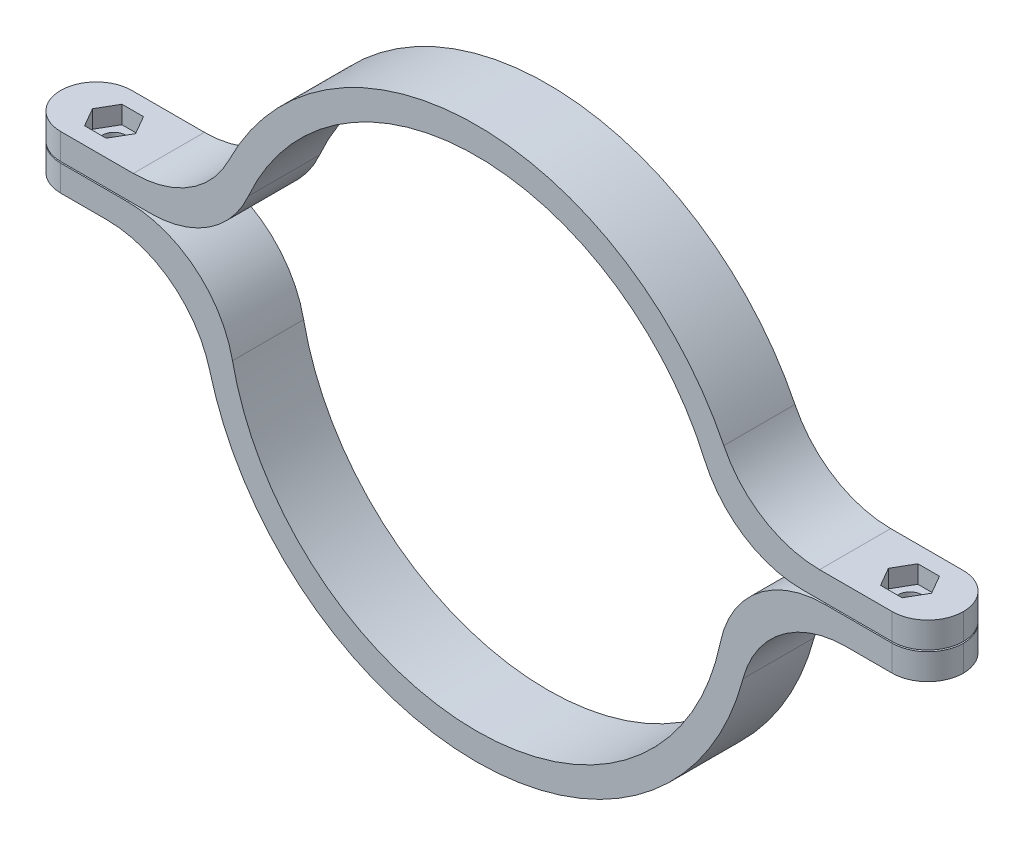
SolidWorks part; units mm, degrees
ref_plane "Front Plane" through (0, 0, 0) normal (0, 0, 1) x (1, 0, 0)
ref_plane "Top Plane" through (0, 0, 0) normal (0, 1, 0) x (1, 0, 0)
ref_plane "Right Plane" through (0, 0, 0) normal (1, 0, 0) x (0, 0, -1)
sketch "Sketch2" plane through (0, 0, 0) normal (0, 0, 1) x (1, 0, 0)
  line L1 (-126.8521, 2.5) -> (126.8521, 2.5)
  line L2 (-126.8521, 2.5) -> (-126.8521, 17.5)
  line L3 (-126.8521, 10) -> (-76.8521, 10)
  line L4 (0, 0) -> (0, 38.05)
  line L5 (-185.0643, 17.5) -> (178.4815, 17.5)
  line L6 (126.8521, 10) -> (76.8521, 10)
  line L7 (126.8521, 2.5) -> (126.8521, 17.5)
  line L8 (-76.8521, 10) -> (76.8521, 10)
  circle A0 centre (0, 0) radius 70 construction
  circle A1 centre (0, 0) radius 70
  circle A2 centre (0, 0) radius 77.5
  circle M7 centre (0, 0) radius 70
  dimension "D2" = 7.5
  dimension "D3" = 50
  dimension "D1" = 7.5
extrude "Boss-Extrude1" add sketch "Sketch2" against normal blind 20 contours A2 M7 | L8 A2 M7 | A2 L3 L2 | A2 L5 L2 L3 | L5 A2 L8 M7 | L5 A2 M7 | L8 A2 L5 M7 | A2 L6 L7 L5 | A2 L7 L6 | A2 L8 M7 region at (-102.0343, 6.2576, 0) region at (-73.4513, 6.2555, 0) region at (-73.7075, 0.7557, 0) region at (-101.5439, 13.7667, 0) region at (-72.4174, 13.7623, 0) region at (0, 75.8752, 0) region at (102.0343, 6.2576, 0) region at (73.4513, 6.2555, 0) region at (72.4174, 13.7623, 0) region at (101.5439, 13.7667, 0)
sketch "Sketch4" plane through (-126.8521, 0, 0) normal (-1, 0, 0) x (0, 0, 1)
  line L0 (-20, 10) -> (0, 10) construction
  line L1 (-20, 9.8) -> (0, 9.8)
  line L2 (-20, 10.2) -> (0, 10.2)
  line L3 (-20, 10.2) -> (-20, 9.8)
  line L4 (0, 2.5) -> (0, 17.5)
  line L5 (0, 17.5) -> (-20, 17.5)
  line L6 (-20, 17.5) -> (-20, 2.5)
  line L7 (-20, 2.5) -> (0, 2.5)
  line L8 (0, 2.5) -> (0, 17.5) construction
  line L9 (0, 17.5) -> (-20, 17.5) construction
  line L10 (-20, 17.5) -> (-20, 2.5) construction
  line L12 (0, 9.8) -> (0, 10.2)
  line L17 (-20, 2.5) -> (0, 2.5)
  point P7 (0, 10)
  line M6 (0, 2.5) -> (0, 17.5)
  line M8 (-20, 17.5) -> (-20, 2.5)
  dimension "D1" = 0
  dimension "D2" = 0.2
  dimension "D3" = 0.2
extrude "Cut-Extrude1" cut sketch "Sketch4" against normal through all both and the other way through all contours L2 L1 M8 M6 region at (-126.8521, 10, -10)
fillet "Fillet1" radius 30 4 edges at (-69.2529, 10.2, -10) (69.2529, 10.2, -10) (75.4983, 17.5, -10) (-75.4983, 17.5, -10)
fillet "Fillet2" radius 30 4 edges at (69.3106, 9.8, -10) (-69.3106, 9.8, -10) (77.4597, 2.5, -10) (-77.4597, 2.5, -10)
fillet "Fillet3" radius 10 4 edges at (-126.8521, 13.85, -20) (-126.8521, 13.85, 0) (126.8521, 13.85, -20) (126.8521, 13.85, 0)
fillet "Fillet4" radius 10 4 edges at (126.8521, 6.15, -20) (126.8521, 6.15, 0) (-126.8521, 6.15, -20) (-126.8521, 6.15, 0)
sketch "Sketch5" plane through (0, 17.5, 0) normal (0, 1, 0) x (1, 0, 0)
  line L12 (-96.4365, 10) -> (96.4365, 10)
  line L13 (96.4365, 10) -> (0, 10)
  line L14 (0, 10) -> (0, 64.3252)
  line L15 (-117.9143, 10.0019) -> (-114.8816, 15.251)
  line L28 (116.8521, 10) -> (111.8521, 10)
  line L29 (114.8816, 15.251) -> (108.8194, 15.249)
  line L30 (108.8194, 15.249) -> (105.79, 9.9981)
  line L31 (105.79, 9.9981) -> (108.8227, 4.749)
  line L32 (108.8227, 4.749) -> (114.8849, 4.751)
  line L33 (114.8849, 4.751) -> (117.9143, 10.0019)
  line L34 (117.9143, 10.0019) -> (114.8816, 15.251)
  line L35 (-114.8849, 4.751) -> (-117.9143, 10.0019)
  line L36 (-108.8227, 4.749) -> (-114.8849, 4.751)
  line L37 (-105.79, 9.9981) -> (-108.8227, 4.749)
  line L38 (-108.8194, 15.249) -> (-105.79, 9.9981)
  line L39 (-114.8816, 15.251) -> (-108.8194, 15.249)
  arc A9 (116.8521, 0) -> (126.8521, 10) centre (116.8521, 10) ccw construction
  arc A10 (116.8521, 0) -> (126.8521, 10) centre (116.8521, 10) ccw
  circle A11 centre (111.8521, 10) radius 5.25 construction
  point P3 (116.3996, 7.3764)
  dimension "D2" = 10.5
  dimension "D3" = 5
extrude "Cut-Extrude2" cut sketch "Sketch5" against normal blind 5 contours L39 L15 L35 L36 L37 L38 | L33 L34 L29 L30 L31 L32 region at (-111.8521, 17.5, -10) region at (116.259, 17.5, -12.5462)
sketch "Sketch6" plane through (0, 17.5, 0) normal (0, 1, 0) x (1, 0, 0)
  line L2 (105.79, 9.9981) -> (117.9143, 10.0019)
  line L3 (-114.8849, 4.751) -> (-108.8194, 15.249) construction
  line L9 (-108.8194, 15.249) -> (-114.8816, 15.251)
  line L10 (-114.8816, 15.251) -> (-117.9143, 10.0019)
  line L11 (-117.9143, 10.0019) -> (-114.8849, 4.751)
  line L18 (-114.8849, 4.751) -> (-108.8227, 4.749)
  line L19 (-108.8227, 4.749) -> (-105.79, 9.9981)
  line L20 (-105.79, 9.9981) -> (-108.8194, 15.249)
  line L21 (-108.8194, 15.249) -> (-114.8816, 15.251)
  line L22 (-114.8816, 15.251) -> (-117.9143, 10.0019)
  line L23 (-117.9143, 10.0019) -> (-114.8849, 4.751)
  line L30 (-114.8849, 4.751) -> (-108.8227, 4.749)
  line L31 (-108.8227, 4.749) -> (-105.79, 9.9981)
  line L32 (114.8849, 4.751) -> (117.9143, 10.0019)
  line L33 (117.9143, 10.0019) -> (114.8816, 15.251)
  line L34 (114.8816, 15.251) -> (108.8194, 15.249)
  line L35 (108.8194, 15.249) -> (105.79, 9.9981)
  line L36 (105.79, 9.9981) -> (108.8227, 4.749)
  line L37 (108.8227, 4.749) -> (114.8849, 4.751)
  line L38 (114.8849, 4.751) -> (117.9143, 10.0019)
  line L39 (117.9143, 10.0019) -> (114.8816, 15.251)
  line L40 (114.8816, 15.251) -> (108.8194, 15.249)
  line L41 (108.8194, 15.249) -> (105.79, 9.9981)
  line L42 (105.79, 9.9981) -> (108.8227, 4.749)
  line L43 (108.8227, 4.749) -> (114.8849, 4.751)
  line L44 (-105.79, 9.9981) -> (-108.8194, 15.249)
  circle A0 centre (-111.8521, 10) radius 3.25
  circle A1 centre (111.8521, 10) radius 3.25
  point P2 (0, 0)
  point P3 (-111.8521, 10)
  point P4 (111.8521, 10)
  dimension "D3" = 6.5
  dimension "D4" = 6.5
  dimension "D1" = 0
  dimension "D5" = 0
extrude "Cut-Extrude3" cut sketch "Sketch6" against normal through all contours A0 | A0 | A1 | A1 region at (111.8517, 17.5, -11.3793) region at (111.8526, 17.5, -8.6207) region at (-111.8521, 17.5, -10)
